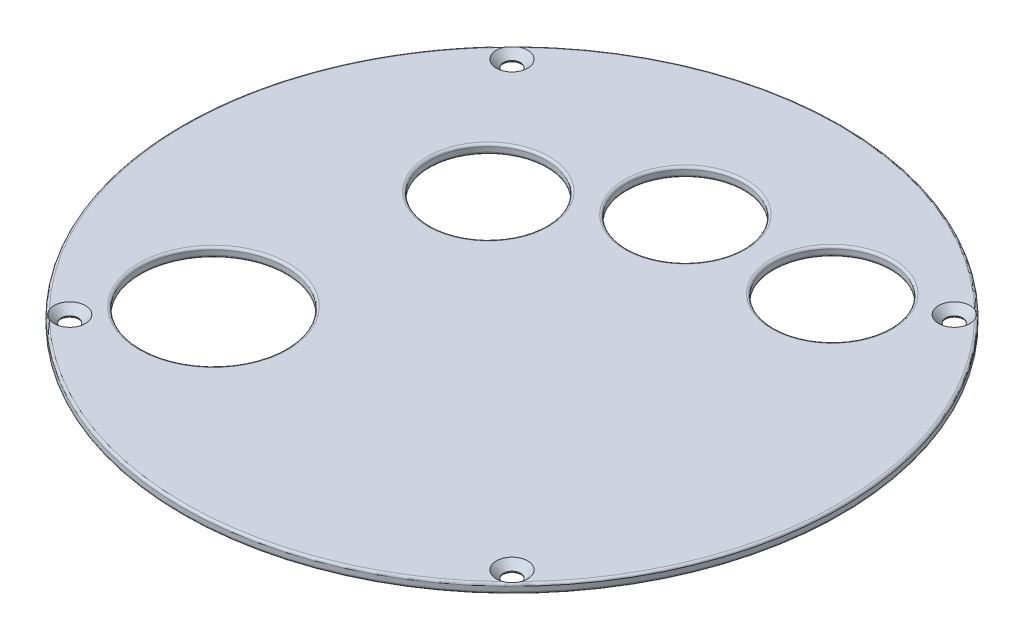
SolidWorks part; units mm, degrees
ref_plane "Front Plane" through (0, 0, 0) normal (0, 0, 1) x (1, 0, 0)
ref_plane "Top Plane" through (0, 0, 0) normal (0, 1, 0) x (1, 0, 0)
ref_plane "Right Plane" through (0, 0, 0) normal (1, 0, 0) x (0, 0, -1)
sketch "Sketch1" plane through (0, 0, 0) normal (0, 1, 0) x (1, 0, 0)
  line L0 (0, 0) -> (-46.669, 46.669) construction
  line L5 (-33, -30) -> (-33, 20) construction
  line L6 (-33, 20) -> (-25, 20) construction
  line L7 (0, 0) -> (46.669, 46.669) construction
  line L8 (0, 0) -> (46.669, -46.669) construction
  line L9 (0, 0) -> (-46.669, -46.669) construction
  line L10 (-25, 20) -> (0, 36.5831) construction
  line L11 (0, 36.5831) -> (30, 37.5831) construction
  line L12 (-25, 20) -> (0, 20) construction
  line L13 (0, 20) -> (0, 36.5831) construction
  line L14 (0, 36.5831) -> (30, 36.5831) construction
  line L15 (30, 36.5831) -> (30, 37.5831)
  line L16 (0, 0) -> (0, 20) construction
  line L17 (-46.669, 46.669) -> (-43.3103, 43.3103) construction
  line L18 (0, 0) -> (69.55, 0) construction
  circle A0 centre (0, 0) radius 69.85 construction
  circle A1 centre (0, 0) radius 69.55
  circle A11 centre (-46.669, 46.669) radius 1.5 construction
  circle A13 centre (-46.669, 46.669) radius 1.8
  circle A14 centre (46.669, 46.669) radius 1.8
  circle A15 centre (46.669, 46.669) radius 1.5 construction
  circle A16 centre (46.669, -46.669) radius 1.8
  circle A17 centre (46.669, -46.669) radius 1.5 construction
  circle A18 centre (-46.669, -46.669) radius 1.8
  circle A19 centre (-46.669, -46.669) radius 1.5 construction
  circle A20 centre (-33, -30) radius 15 construction
  circle A21 centre (-25, 20) radius 12 construction
  circle A22 centre (0, 36.5831) radius 12 construction
  circle A23 centre (30, 37.5831) radius 12 construction
  circle A25 centre (-25, 20) radius 12.3
  circle A26 centre (0, 36.5831) radius 12.3
  circle A27 centre (30, 37.5831) radius 12.3
  circle A28 centre (-33, -30) radius 15.3
  circle A30 centre (30, 37.5831) radius 13 construction
  circle A31 centre (-33, -30) radius 17 construction
  circle A32 centre (0, 0) radius 62.5 construction
  point P40 (0, 0)
  dimension "D1" = 139.7
  dimension "D5" = 24
  dimension "D7" = 30
  dimension "D9" = 3
  dimension "D6" = 30
  dimension "D17" = 34
  dimension "D18" = 26
  dimension "D19" = 125
  dimension "D20" = 45
  dimension "D3" = 50
  dimension "D4" = 8
  dimension "D8" = 30
  dimension "D11" = 66
  dimension "D13" = 25
  dimension "D14" = 1
  dimension "D15" = 20
  dimension "D2" = 0.3
  dimension "D10" = 0.3
  dimension "D16" = 0.3
  dimension "D12" = 4
extrude "Boss-Extrude1" add sketch "Sketch1" along normal blind 2 contours A1 region at (1.6847, 0, 1.7464)
chamfer "Chamfer3" distance 1.5 angle 45 4 edges at (-46.669, 2, -44.869) (46.669, 2, 48.469) (-46.669, 2, 48.469) (46.669, 2, -44.869)
fillet "Fillet1" radius 0.5 14 edges at (-46.669, 0, -44.869) (46.669, 0, -44.869) (46.669, 0, 48.469) (-46.669, 0, 48.469) (-33, 0, 45.3) (-33, 2, 45.3) (30, 0, -25.2831) (30, 2, -25.2831) (0, 0, -24.2831) (0, 2, -24.2831) (-25, 0, -7.7) (-25, 2, -7.7) (0, 0, 69.55) (0, 2, 69.55)
